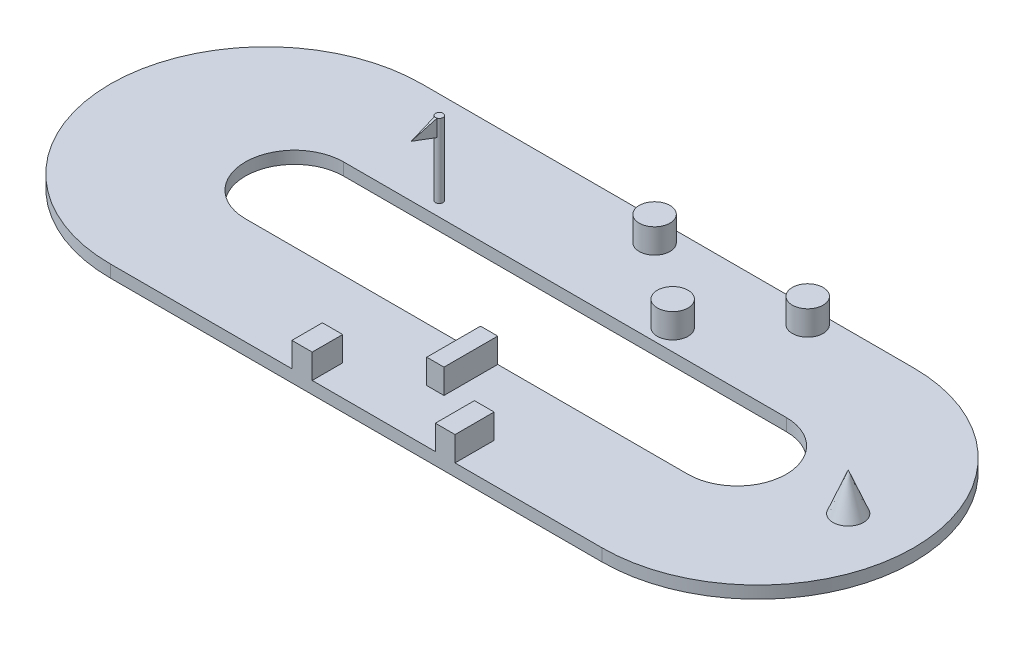
SolidWorks part; units mm, degrees
ref_plane "Front Plane" through (0, 0, 0) normal (0, 0, 1) x (1, 0, 0)
ref_plane "Top Plane" through (0, 0, 0) normal (0, 1, 0) x (1, 0, 0)
ref_plane "Right Plane" through (0, 0, 0) normal (1, 0, 0) x (0, 0, -1)
sketch "Sketch1" plane through (0, 0, 0) normal (0, 1, 0) x (1, 0, 0)
  line L4 (-6645.6009, 3345.3119) -> (13354.3991, 3345.3119)
  line L5 (-5491.5943, -991.6424) -> (12508.4057, -991.6424)
  line L6 (-5491.5943, -4991.6424) -> (12508.4057, -4991.6424)
  line L7 (-6645.6009, -9328.5967) -> (13354.3991, -9328.5967)
  arc A0 (-5491.5943, -4991.6424) -> (-5491.5943, -991.6424) centre (-5491.5943, -2991.6424) cw
  arc A1 (12508.4057, -4991.6424) -> (12508.4057, -991.6424) centre (12508.4057, -2991.6424) ccw
  arc A2 (13354.3991, 3345.3119) -> (13354.3991, -9328.5967) centre (13354.3991, -2991.6424) cw
  arc A3 (-6645.6009, 3345.3119) -> (-6645.6009, -9328.5967) centre (-6645.6009, -2991.6424) ccw
  dimension "D1" = 4000
  dimension "D2" = 12673.9086
  dimension "D3" = 18000
  dimension "D4" = 20000
extrude "Boss-Extrude1" add sketch "Sketch1" along normal blind 500
sketch "Sketch2" plane through (0, 500, 0) normal (0, 1, 0) x (1, 0, 0)
  line L0 (-6645.6009, -9328.5967) -> (13354.3991, -9328.5967) construction
  line L1 (6574.9392, -9328.5967) -> (7375.1667, -9328.5967)
  line L2 (6574.9392, -9328.5967) -> (6574.9392, -7739.7139)
  line L3 (6574.9392, -7739.7139) -> (7375.1667, -7739.7139)
  line L4 (7375.1667, -9328.5967) -> (7375.1667, -7739.7139)
  line L6 (4074.2283, -4991.6424) -> (4774.4274, -4991.6424)
  line L7 (4074.2283, -4991.6424) -> (4074.2283, -7178.9806)
  line L8 (4074.2283, -7178.9806) -> (4774.4274, -7178.9806)
  line L9 (4774.4274, -4991.6424) -> (4774.4274, -7178.9806)
  line L10 (-5491.5943, -4991.6424) -> (12508.4057, -4991.6424) construction
  line L12 (740.52, -9328.5967) -> (1565.7546, -9328.5967)
  line L13 (740.52, -9328.5967) -> (740.52, -8089.8134)
  line L14 (740.52, -8089.8134) -> (1565.7546, -8089.8134)
  line L15 (1565.7546, -9328.5967) -> (1565.7546, -8089.8134)
  circle A0 centre (3674.1146, 2488.1934) radius 625
  circle A1 centre (7029.5233, -131.3386) radius 625
  circle A2 centre (9675.8206, 2713.2574) radius 625
  point P18 (7029.5233, -131.3386)
  dimension "D1" = 1250
extrude "Boss-Extrude2" add sketch "Sketch2" along normal blind 1000
sketch "Sketch3" plane through (0, 500, 0) normal (0, 1, 0) x (1, 0, 0)
  circle A0 centre (17154.9805, -3118.0487) radius 622.677
extrude "Boss-Extrude3" add sketch "Sketch3" along normal blind 3000 draft 22
sketch "Sketch4" plane through (0, 500, 0) normal (0, 1, 0) x (1, 0, 0)
  line L0 (-3644.4792, 3345.3119) -> (-3644.4792, -991.6424) construction
  line L1 (13354.3991, 3345.3119) -> (-6645.6009, 3345.3119) construction
  line L2 (12508.4057, -991.6424) -> (-5491.5943, -991.6424) construction
  text T0 "START" font "Century Gothic" height in points 72
sketch "Sketch5" plane through (0, 500, 0) normal (0, 1, 0) x (1, 0, 0)
  circle A0 centre (-2186.3823, -408.6891) radius 150.6346
  point P2 (-2186.3823, -408.6891)
  point P4 (-3644.4792, 161.6093)
extrude "Boss-Extrude4" add sketch "Sketch5" along normal blind 3000
ref_plane "Plane1" through (0, 0, 559.3237) normal (0, 0, 1) x (1, 0, 0)
sketch "Sketch6" plane through (0, 0, 559.3237) normal (0, 0, 1) x (1, 0, 0)
  line L0 (-2035.7477, 3500) -> (-2337.0169, 3500) construction
  line L1 (-2236.4558, 3500) -> (-2132.2084, 3500)
  line L2 (-2236.4558, 3500) -> (-2236.4558, 2819.8905)
  line L3 (-2236.4558, 2819.8905) -> (-2132.2084, 2819.8905)
  line L4 (-2132.2084, 3500) -> (-2132.2084, 2819.8905)
extrude "Boss-Extrude5" add sketch "Sketch6" along normal blind 1000 draft 3 separate body
ref_plane "Plane2" through (-2035.7477, 0, 0) normal (1, 0, 0) x (0, 0, -1)
sketch "Sketch8" plane through (-2035.7477, 0, 0) normal (1, 0, 0) x (0, 0, -1)
  line L0 (-559.3237, 3500) -> (-559.3237, 2819.8905)
  line L1 (-559.3237, 2819.8905) -> (-1553.903, 3159.9452)
  line L2 (-1553.903, 2872.0142) -> (-1553.903, 3447.8763) construction
  line L3 (-1553.903, 3159.9452) -> (-559.3237, 3500)
  line L4 (-559.3237, 3500) -> (-1553.903, 3447.8763)
  line L5 (-1553.903, 3447.8763) -> (-1553.903, 3159.9452)
  line L6 (-559.3237, 2819.8905) -> (-1553.903, 2872.0142)
  line L7 (-1553.903, 2872.0142) -> (-1553.903, 3159.9452)
extrude "Cut-Extrude1" cut sketch "Sketch8" against normal blind 1000 contours L4 L5 L3 | L7 L6 L1 region at (-2035.7477, 3369.2738, 1222.3766) region at (-2035.7477, 2950.6166, 1222.3766)
sketch "Sketch9" plane through (0, 0, 559.3237) normal (0, 0, -1) x (-1, 0, 0)
  line L4 (2236.4558, 2819.8905) -> (2236.4558, 3500)
  line L5 (2236.4558, 3500) -> (2132.2084, 3500)
  line L6 (2132.2084, 3500) -> (2132.2084, 2819.8905)
  line L7 (2132.2084, 2819.8905) -> (2236.4558, 2819.8905)
  line L8 (2236.4558, 2819.8905) -> (2236.4558, 3500)
  line L9 (2236.4558, 3500) -> (2132.2084, 3500)
  line L10 (2132.2084, 3500) -> (2132.2084, 2819.8905)
  line L11 (2132.2084, 2819.8905) -> (2236.4558, 2819.8905)
  dimension "D1" = 0
extrude "Boss-Extrude6" add sketch "Sketch9" along normal blind 50
